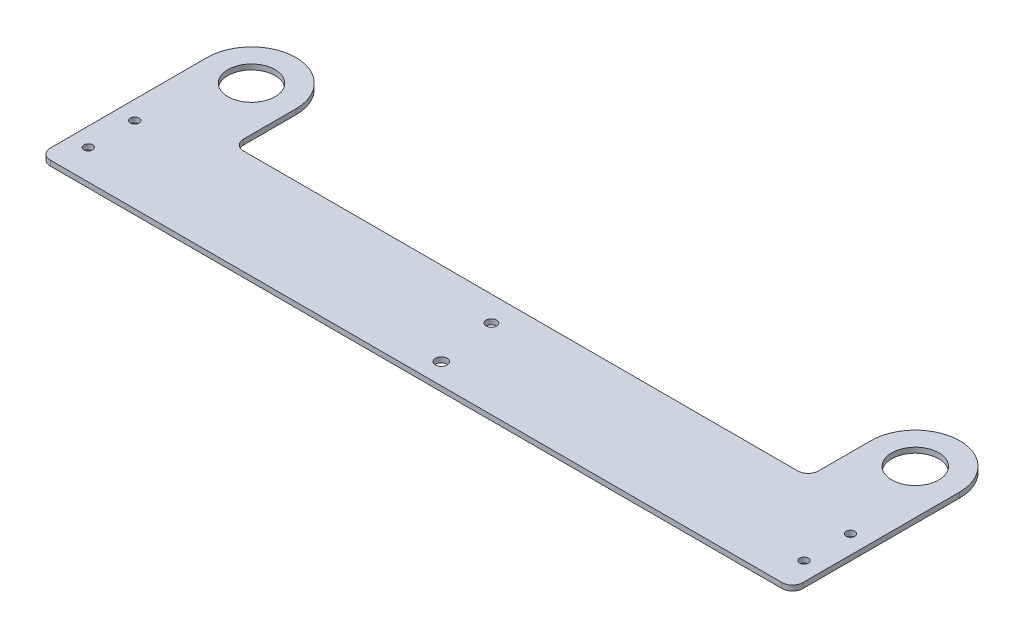
SolidWorks part; units mm, degrees
material "6063-T6"
ref_plane "Front" through (0, 0, 0) normal (0, 0, 1) x (1, 0, 0)
ref_plane "Top" through (0, 0, 0) normal (0, 1, 0) x (1, 0, 0)
ref_plane "Right" through (0, 0, 0) normal (1, 0, 0) x (0, 0, -1)
sketch "Sketch1" plane through (0, 0, 0) normal (0, 1, 0) x (1, 0, 0)
  line L0 (0, 0) -> (403.225, 0) construction
  line L5 (-26.9875, 0) -> (-26.9875, -95.25)
  line L6 (430.2125, 0) -> (430.2125, -95.25)
  line L7 (423.8625, -101.6) -> (-20.6375, -101.6)
  line L8 (26.9875, 0) -> (26.9875, -31.75)
  line L9 (376.2375, 0) -> (376.2375, -31.75)
  line L10 (369.8875, -38.1) -> (33.3375, -38.1)
  circle A0 centre (0, 0) radius 14.2875
  circle A1 centre (403.225, 0) radius 14.2875
  arc A2 (26.9875, 0) -> (-26.9875, 0) centre (0, 0) ccw
  arc A3 (430.2125, 0) -> (376.2375, 0) centre (403.225, 0) ccw
  circle A4 centre (0, 0) radius 26.9875 construction
  circle A5 centre (403.225, 0) radius 26.9875 construction
  arc A6 (376.2375, -31.75) -> (369.8875, -38.1) centre (369.8875, -31.75) cw
  arc A7 (430.2125, -95.25) -> (423.8625, -101.6) centre (423.8625, -95.25) cw
  arc A8 (-26.9875, -95.25) -> (-20.6375, -101.6) centre (-20.6375, -95.25) ccw
  arc A9 (26.9875, -31.75) -> (33.3375, -38.1) centre (33.3375, -31.75) ccw
  point P24 (-26.9875, -101.6)
  point P27 (26.9875, -38.1)
  dimension "D3" = 28.575
  dimension "D5" = 28.575
  dimension "D7" = 6.35
  dimension "D1" = 12.7
  dimension "D2" = 101.6
  dimension "D4" = 403.225
  dimension "D6" = 38.1
extrude "Boss-Extrude1" add sketch "Sketch1" along normal blind 3.175
sketch "Sketch2" plane through (0, 3.175, 0) normal (0, 1, 0) x (1, 0, 0)
  line L1 (-26.9875, 0) -> (-26.9875, -95.25) construction
  line L2 (-20.6375, -101.6) -> (423.8625, -101.6) construction
  line L3 (430.2125, -95.25) -> (430.2125, 0) construction
  circle A1 centre (204.1525, -88.9) radius 3.556
  circle A3 centre (199.0725, -53.34) radius 3.175
  dimension "D3" = 231.14
  dimension "D1" = 231.14
  dimension "D2" = 12.7
  dimension "D4" = 48.26
extrude "Cut-Extrude1" cut sketch "Sketch2" against normal up to next
sketch "Sketch3" plane through (0, 3.175, 0) normal (0, 1, 0) x (1, 0, 0)
  line L0 (201.6125, -38.1) -> (201.6125, 7.4644) construction
  line L1 (369.8875, -38.1) -> (33.3375, -38.1) construction
  circle A1 centre (-15.7797, -55.159) radius 2.667
  circle A2 centre (419.0047, -55.159) radius 2.667
  circle A3 centre (-15.7797, -83.3715) radius 2.667
  circle A4 centre (419.0047, -83.3715) radius 2.667
  dimension "D1" = 5.334
extrude "Cut-Extrude2" cut sketch "Sketch3" against normal up to next
